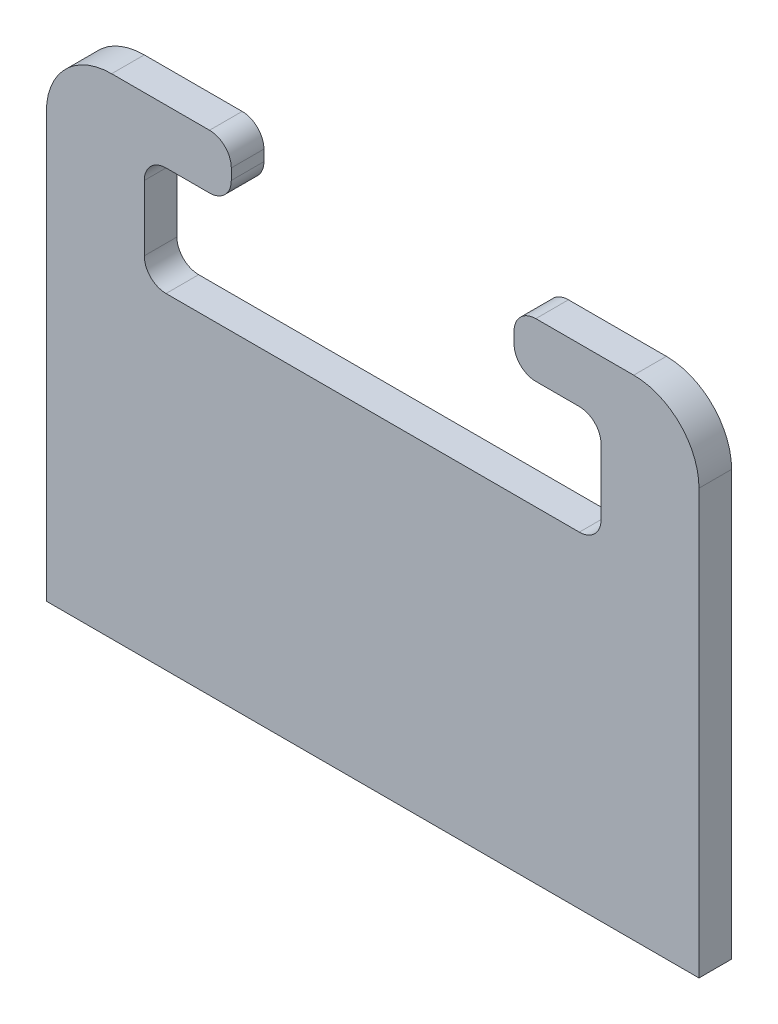
SolidWorks part; units mm, degrees
ref_plane "前视基准面" through (0, 0, 0) normal (0, 0, 1) x (1, 0, 0)
ref_plane "上视基准面" through (0, 0, 0) normal (0, 1, 0) x (1, 0, 0)
ref_plane "右视基准面" through (0, 0, 0) normal (1, 0, 0) x (0, 0, -1)
other "Configuration Table"
sketch "草图1" plane through (0, 0, 0) normal (0, 0, 1) x (1, 0, 0)
  line L0 (13, 22.5) -> (30, 22.5)
  line L1 (-30, 22.5) -> (-13, 22.5)
  line L2 (-30, 22.5) -> (-30, -22.5)
  line L3 (-30, -22.5) -> (30, -22.5)
  line L4 (30, 22.5) -> (30, -22.5)
  line L5 (-30, 22.5) -> (30, -22.5) construction
  line L6 (-30, -22.5) -> (30, 22.5) construction
  line L8 (13, 22.5) -> (13, 17.5)
  line L10 (-13, 22.5) -> (-13, 17.5)
  line L11 (21, 17.5) -> (13, 17.5)
  line L12 (21, 17.5) -> (21, 7.5)
  line L13 (21, 7.5) -> (-21, 7.5)
  line L14 (-21, 17.5) -> (-21, 7.5)
  line L15 (-13, 17.5) -> (-21, 17.5)
  point P0 (0, 0)
  dimension "D1" = 45
  dimension "D2" = 60
  dimension "D3" = 5
  dimension "D4" = 17
  dimension "D5" = 17
  dimension "D6" = 9
  dimension "D7" = 9
  dimension "D8" = 10
extrude "凸台-拉伸1" add sketch "草图1" along normal blind 3
fillet "圆角1" radius 6 2 edges at (30, 22.5, 1.5) (-30, 22.5, 1.5)
fillet "圆角2" radius 2 8 edges at (21, 17.5, 1.5) (21, 7.5, 1.5) (-21, 7.5, 1.5) (-21, 17.5, 1.5) (-13, 17.5, 1.5) (-13, 22.5, 1.5) (13, 17.5, 1.5) (13, 22.5, 1.5)
